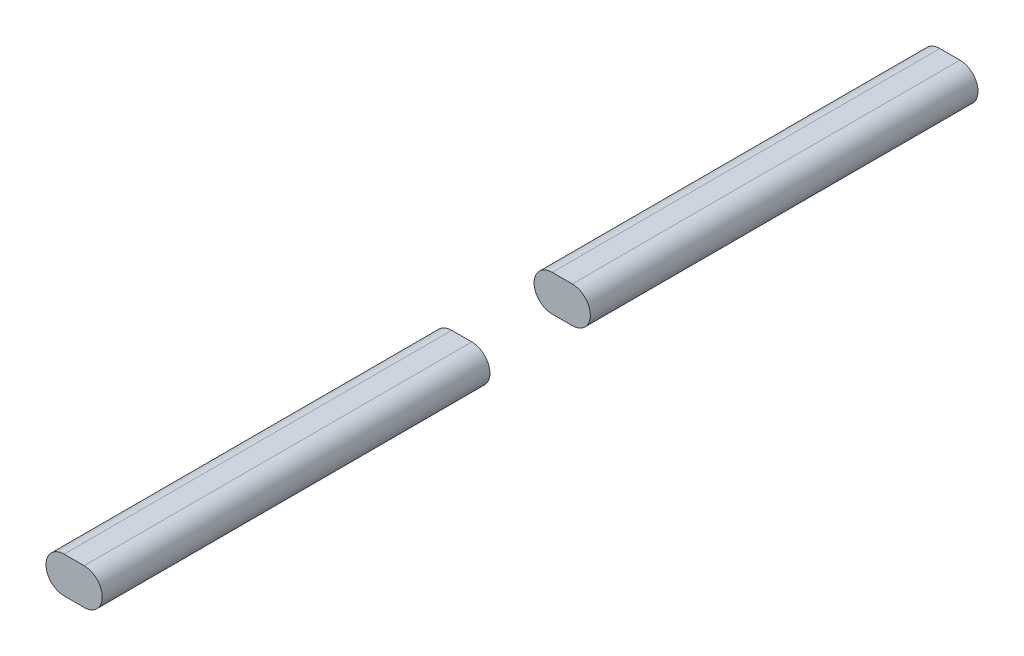
SolidWorks part; units mm, degrees
note: The reader was unsure of these and kept them because the rebuilt part matched: shared geometry of "Эскиз1<2>".
material "Неопрен"
ref_plane "Спереди" through (0, 0, 0) normal (0, 0, 1) x (1, 0, 0)
ref_plane "Сверху" through (0, 0, 0) normal (0, 1, 0) x (1, 0, 0)
ref_plane "Справа" through (0, 0, 0) normal (1, 0, 0) x (0, 0, -1)
sketch "Эскиз1" plane through (0, 0, 0) normal (0, 0, 1) x (1, 0, 0)
  line L0 (-27.75, -4.5) -> (-22.75, -4.5) construction
  line L2 (-27.75, 0) -> (-22.75, 0)
  line L3 (-27.75, -9) -> (-22.75, -9)
  line L4 (-11, 0) -> (-22.75, 0) construction
  line L5 (-22.75, -9) -> (22.75, -9) construction
  arc A0 (-27.75, 0) -> (-27.75, -9) centre (-27.75, -4.5) ccw
  arc A1 (-22.75, -9) -> (-22.75, 0) centre (-22.75, -4.5) ccw
  point P4 (-25.25, -4.5)
  point P12 (-45.652, 1.8969)
  point P13 (0, 0)
  dimension "D1" = 5
  dimension "D2" = 25.25
  dimension "D3" = 4.5
extrude "Бобышка-Вытянуть1" add sketch "Эскиз1" against normal up to surface (96.5 mm away) from surface at -12.5
extrude "Бобышка-Вытянуть2" add sketch "Эскиз1<2>" along normal up to surface (96.5 mm away) from surface at 12.5 separate body
sketch "Эскиз1<2>" plane through (0, 0, 0) normal (0, 0, 1) x (1, 0, 0) same geometry as "Эскиз1"
